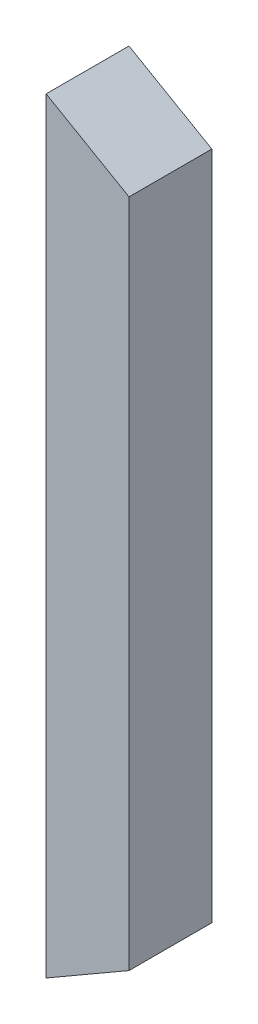
SolidWorks part; units mm, degrees
ref_plane "Plan de face" through (0, 0, 0) normal (0, 0, 1) x (1, 0, 0)
ref_plane "Plan de dessus" through (0, 0, 0) normal (0, 1, 0) x (1, 0, 0)
ref_plane "Plan de droite" through (0, 0, 0) normal (1, 0, 0) x (0, 0, -1)
sketch "Esquisse1" plane through (0, 0, 0) normal (0, 0, 1) x (1, 0, 0)
  line L1 (0, 0) -> (60, 0)
  line L2 (0, 0) -> (0, 520)
  line L3 (0, 520) -> (60, 520)
  line L4 (60, 0) -> (60, 520)
  dimension "D1" = 520
  dimension "D2" = 60
extrude "Boss.-Extru.1" add sketch "Esquisse1" along normal blind 60
sketch "Esquisse2" plane through (0, 0, 60) normal (0, 0, 1) x (1, 0, 0)
  line L0 (60, 0) -> (0, 0)
  line L1 (0, 0) -> (0, -34.641)
  line L2 (0, -34.641) -> (60, 0)
  dimension "D1" = 30
extrude "Boss.-Extru.2" add sketch "Esquisse2" against normal up to vertex (60 mm away) up to point (60, 0, 0)
sketch "Esquisse3" plane through (0, 0, 60) normal (0, 0, 1) x (1, 0, 0)
  line L0 (60, 485.359) -> (0, 520)
  line L1 (60, 0) -> (60, 520) construction
  line L2 (0, 520) -> (60, 520)
  line L3 (60, 520) -> (60, 485.359)
  dimension "D1" = 30
extrude "Enlèv. mat.-Extru.1" cut sketch "Esquisse3" against normal through all both and the other way through all
